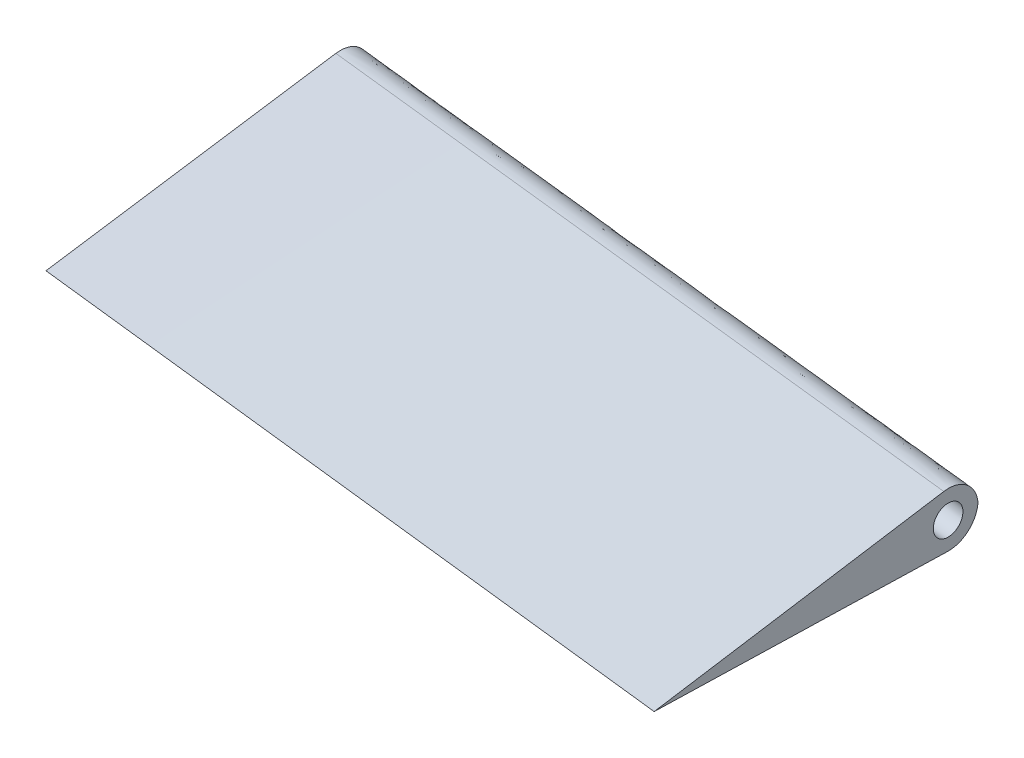
SolidWorks part; units mm, degrees
material "PET"
ref_plane "Alzado" through (0, 0, 0) normal (0, 0, 1) x (1, 0, 0)
ref_plane "Planta" through (0, 0, 0) normal (0, 1, 0) x (1, 0, 0)
ref_plane "Vista lateral" through (0, 0, 0) normal (1, 0, 0) x (0, 0, -1)
sketch "Croquis1" plane through (0, 0, 0) normal (1, 0, 0) x (0, 0, -1)
  line L0 (27.5001, 5.1042) -> (27.5001, -5.1042)
  line L1 (27.5001, -5.1042) -> (-27.5001, -3.1123)
  line L2 (-27.5001, -3.1123) -> (27.5001, 5.1042)
ref_plane "Plano1" through (115.97, 0, 0) normal (1, 0, 0) x (0, 0, -1)
sketch "Croquis2" plane through (115.97, 0, 0) normal (1, 0, 0) x (0, 0, -1)
  line L0 (14.7901, 5.1042) -> (14.7901, -5.1042)
  line L1 (14.7901, -5.1042) -> (-40.2101, -3.5928)
  line L2 (-40.2101, -3.5928) -> (14.7901, 5.1042)
  line L4 (27.5001, 5.1042) -> (5.9268, 5.1042) construction
  dimension "D1" = 12.71
  dimension "D2" = 10.2085
loft "Recubrir1" add profiles "Croquis1", "Croquis2" connector at (0, 5.1042, -27.5001) connector at (115.97, 5.1042, -14.7901)
fillet "Redondeo1" radius 5 2 edges
ref_plane "Plano3" through (115.97, 4.184, -8.9702) normal (-0.994, 0.0005, -0.1093) x (-0.1093, 0.0001, 0.994)
sketch "Croquis3" plane through (-114.2926, -9.4134, 2084.9409) normal (-0.994, 0.0005, -0.1093) x (-0.1093, -0.009, 0.994)
  line L0 (-2107.049, -14.5293) -> (-2107.049, -5.3237) construction
  circle A0 centre (-2107.2569, -9.949) radius 2.5
  spline S0 degree 3 poles (-2106.5709, -5.3679) (-2106.912, -5.3198) (-2107.2522, -5.3074) (-2107.9304, -5.3512) (-2108.2724, -5.4088) (-2108.9305, -5.5907) (-2109.2472, -5.7142) (-2109.7035, -5.9483) (-2109.8532, -6.0351) (-2110.1408, -6.2223) (-2110.2788, -6.3227) (-2110.6761, -6.6437) (-2110.9192, -6.8846) (-2111.3568, -7.4191) (-2111.5446, -7.7044) (-2111.8604, -8.3101) (-2111.9891, -8.6346) (-2112.1747, -9.294) (-2112.2331, -9.6297) (-2112.2569, -9.9716) knots 0 0 0 0 0.125 0.125 0.25 0.25 0.375 0.375 0.4375 0.4375 0.5 0.5 0.625 0.625 0.75 0.75 0.875 0.875 1 1 1 1 construction
  dimension "D1" = 5
ref_plane "Plano2" through (108.19, 0, 0) normal (1, 0, 0) x (0, 0, -1)
sketch "Croquis5" plane through (108.19, 0, 0) normal (1, 0, 0) x (0, 0, -1)
  line L0 (-23.6526, -3.3921) -> (-25.6526, -3.3921)
  line L2 (-23.6526, -3.3921) -> (-23.6526, -4.901)
  line L5 (-25.6526, -3.3921) -> (-25.6526, -5.731)
  line L6 (-25.3597, -6.4381) -> (-22.2392, -9.5586)
  line L7 (-20.825, -9.5586) -> (-20.8242, -9.5578)
  line L8 (-20.8242, -8.1436) -> (-23.3597, -5.6081)
  arc A0 (-20.825, -9.5586) -> (-22.2392, -9.5586) centre (-21.5321, -8.8515) cw
  arc A1 (-20.8242, -9.5578) -> (-20.8242, -8.1436) centre (-21.5313, -8.8507) ccw
  arc A2 (-23.3597, -5.6081) -> (-23.6526, -4.901) centre (-22.6526, -4.901) cw
  arc A3 (-25.6526, -5.731) -> (-25.3597, -6.4381) centre (-24.6526, -5.731) ccw
  point P12 (-23.6526, -5.3152)
  dimension "D3" = 1
  dimension "D5" = 1
  dimension "D1" = 2.0011
  dimension "D2" = 2
  dimension "D4" = 4
extrude "Saliente-Extruir1" add sketch "Croquis5" along normal mid plane 2
sketch "Croquis8" plane through (107.19, 0, 0) normal (-1, 0, 0) x (0, 0, 1)
  circle A0 centre (21.5313, -8.8507) radius 1.0011
extrude "Saliente-Extruir2" add sketch "Croquis8" along normal blind 4
extrude "Cortar-Extruir1" cut sketch "Croquis3" against normal through all both and the other way through all
